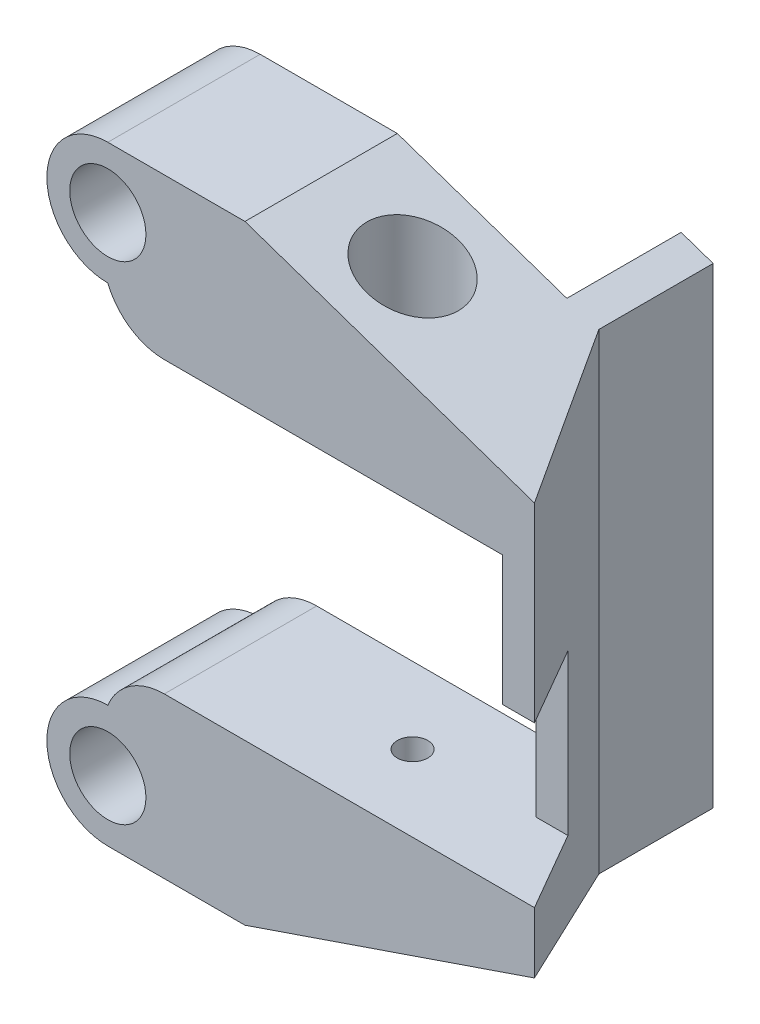
SolidWorks part; units mm, degrees
ref_plane "Alzado" through (0, 0, 0) normal (0, 0, 1) x (1, 0, 0)
ref_plane "Planta" through (0, 0, 0) normal (0, 1, 0) x (1, 0, 0)
ref_plane "Vista lateral" through (0, 0, 0) normal (1, 0, 0) x (0, 0, -1)
sketch "Croquis1" plane through (0, 0, 0) normal (0, 0, 1) x (1, 0, 0)
  line L5 (-103.2316, 22.7007) -> (-131.2316, 22.7007)
  line L6 (-131.2316, 22.7007) -> (-131.2316, 20.2007)
  line L7 (-103.2316, 22.7007) -> (-103.2316, 18.7007)
  line L8 (-103.2316, 18.7007) -> (-125.2316, 18.7007)
  line L9 (-125.2316, 18.7007) -> (-125.2316, 12.2007)
  line L10 (-125.2316, 12.2007) -> (-131.2316, 12.2007)
  circle A0 centre (-131.2316, 16.2007) radius 2.5
  arc A2 (-131.2316, 20.2007) -> (-131.2316, 12.2007) centre (-131.2316, 16.2007) ccw
  dimension "D1" = 4
  dimension "D2" = 5
  dimension "D3" = 6
  dimension "D9" = 1.5
  dimension "D7" = 4
  dimension "D4" = 6.5
  dimension "D5" = 28
  dimension "D6" = 6.5
  dimension "D8" = 2.5
extrude "Saliente-Extruir1" add sketch "Croquis1" along normal blind 10
sketch "Croquis2" plane through (0, 18.7007, 0) normal (0, -1, 0) x (1, 0, 0)
  line L1 (-103.2316, 0) -> (-103.2316, 10)
  line L2 (-103.2316, 10) -> (-109.0051, 0)
  line L4 (-109.0051, 0) -> (-103.2316, 0)
  line L6 (-103.2316, 10) -> (-103.2316, 0) construction
  circle A0 centre (-116.2316, 5) radius 1
  dimension "D1" = 13
  dimension "D2" = 30
  dimension "D3" = 0
extrude "Cortar-Extruir1" cut sketch "Croquis2" against normal up to vertex (4 mm away) up to point (-103.2316, 22.7007, 10)
sketch "Croquis3" plane through (0, 18.7007, 0) normal (0, -1, 0) x (1, 0, 0)
  line L0 (-103.2316, 10) -> (-105.3316, 10)
  line L1 (-105.3316, 10) -> (-111.1051, 0)
  line L2 (-111.1051, 0) -> (-109.0051, 0)
  line L3 (-103.2316, 10) -> (-109.0051, 0)
  dimension "D1" = 2.1
  dimension "D2" = 2.1
extrude "Saliente-Extruir2" add sketch "Croquis3" against normal blind 13.5
sketch "Croquis4" plane through (0, 18.7007, 0) normal (0, -1, 0) x (1, 0, 0)
  circle A0 centre (-116.2316, 5) radius 3
extrude "Cortar-Extruir2" cut sketch "Croquis4" against normal blind 1
sketch "Croquis6" plane through (0, 18.7007, 0) normal (0, -1, 0) x (1, 0, 0)
  line L0 (-125.2316, 10) -> (-103.2316, 10)
  line L1 (-103.2316, 10) -> (-109.0051, 0)
  line L2 (-109.0051, 0) -> (-125.2316, 0)
  line L3 (-125.2316, 0) -> (-125.2316, 10)
  circle A0 centre (-116.2316, 5) radius 3
extrude "Saliente-Extruir3" add sketch "Croquis6" along normal up to vertex (6.5 mm away) up to point (-125.2316, 12.2007, 10)
sketch "Croquis7" plane through (0, 0, 10) normal (0, 0, 1) x (1, 0, 0)
  line L1 (-103.2316, 12.2007) -> (-103.2316, 32.2007) construction
  line L4 (-103.2316, 18.7007) -> (-103.2316, 12.2007)
  line L5 (-103.2316, 12.2007) -> (-122.2316, 12.2007)
  line L6 (-131.2316, 12.2007) -> (-103.2316, 12.2007) construction
  line L7 (-122.2316, 12.2007) -> (-103.2316, 18.7007)
  dimension "D1" = 19
  dimension "D2" = 6.5
extrude "Cortar-Extruir4" cut sketch "Croquis7" against normal blind 10
sketch "Croquis5" plane through (0, 0, 10) normal (0, 0, 1) x (1, 0, 0)
  line L0 (-103.2316, 18.7007) -> (-103.2316, 32.2007) construction
  line L1 (-105.3316, 22.7007) -> (-103.2316, 22.7007)
  line L2 (-105.3316, 22.7007) -> (-105.3316, 33.2007)
  line L3 (-105.3316, 33.2007) -> (-103.2316, 33.2007)
  line L4 (-103.2316, 22.7007) -> (-103.2316, 33.2007)
  dimension "D1" = 10.5
sketch "Croquis8" plane through (0, 0, 0) normal (0, 0, -1) x (-1, 0, 0)
  line L0 (109.0051, 16.7255) -> (109.0051, 32.2007)
  line L1 (109.0051, 32.2007) -> (111.1051, 32.2007)
  line L2 (111.1051, 32.2007) -> (111.1051, 22.7007)
  line L3 (111.1051, 22.7007) -> (111.1051, 16.0071)
  line L4 (109.0051, 16.7255) -> (122.2316, 12.2007) construction
  line L5 (111.1051, 16.0071) -> (109.0051, 16.7255)
extrude "Saliente-Extruir4" add sketch "Croquis8" along normal blind 7.5
mirror "Simetría1" about plane through (0, 32.2007, 0) normal (0, -1, 0) of bodies 110
extrude "Cortar-Extruir5" cut sketch "Croquis5" along direction (-0.5, 0, -0.866) on the side against the normal blind 6
fillet "Redondeo1" radius 4 2 edges at (-131.2316, 41.7007, 5) (-131.2316, 22.7007, 5)
sketch "Croquis9" plane through (0, 12.2007, 0) normal (0, -1, 0) x (1, 0, 0)
  text T0 "30º"
extrude "Cortar-Extruir6" cut sketch "Croquis9" against normal blind 1
